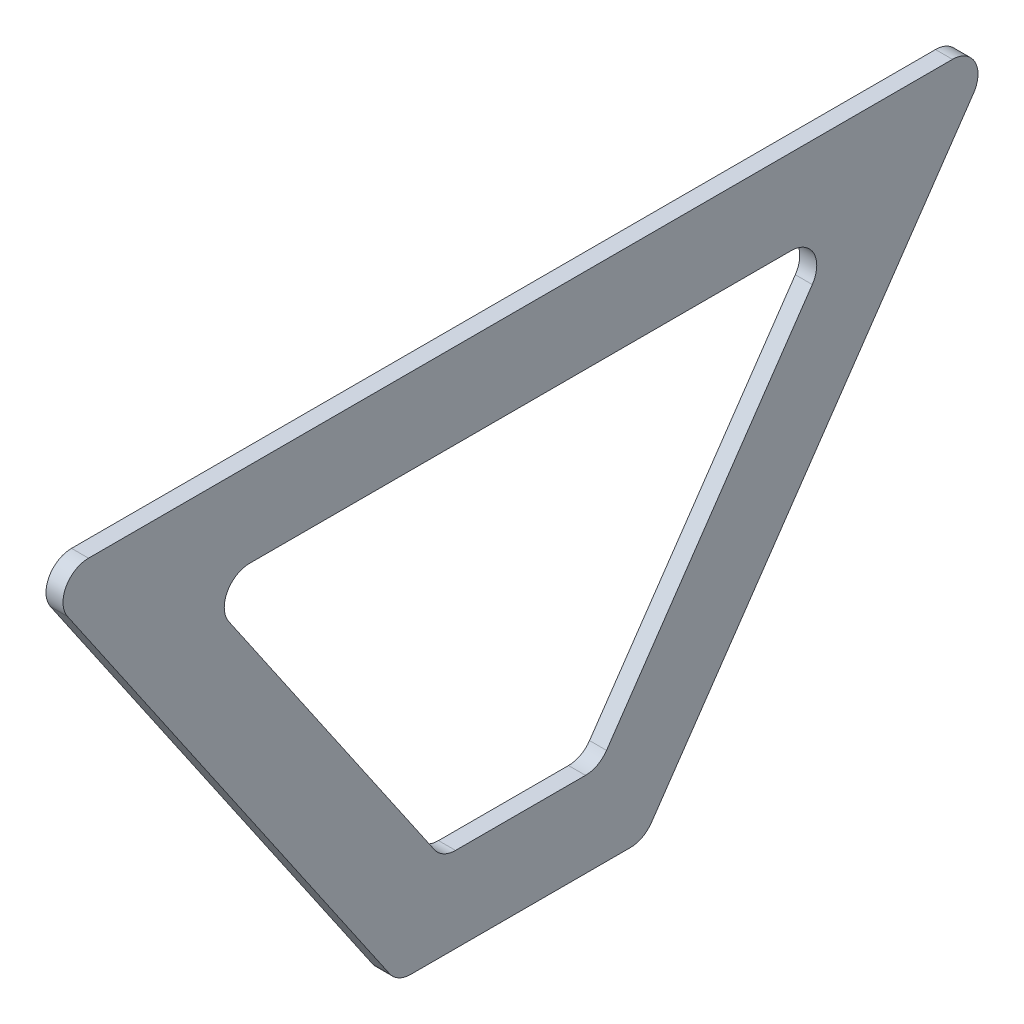
SolidWorks part; units mm, degrees
material "Acrylic (Medium-high impact)"
ref_plane "Front Plane" through (0, 0, 0) normal (0, 0, 1) x (1, 0, 0)
ref_plane "Top Plane" through (0, 0, 0) normal (0, 1, 0) x (1, 0, 0)
ref_plane "Right Plane" through (0, 0, 0) normal (1, 0, 0) x (0, 0, -1)
sketch "Sketch1" plane through (0, 0, 0) normal (1, 0, 0) x (0, 0, -1)
  line L0 (0, 24.4397) -> (0, -31.8822) construction
  line L1 (-14.5, -22.0259) -> (14.5, -22.0259)
  line L2 (14.5, -22.0259) -> (56.5, 39.3247)
  line L3 (56.5, 39.3247) -> (-56.5, 39.3247)
  line L4 (-9.2271, -12.0259) -> (9.2271, -12.0259)
  line L5 (9.2271, -12.0259) -> (37.5353, 29.3247)
  line L6 (37.5353, 29.3247) -> (-37.5353, 29.3247)
  line L7 (-9.2271, -12.0259) -> (-37.5353, 29.3247)
  line L8 (-14.5, -22.0259) -> (-56.5, 39.3247)
  point P13 (0, 29.3247)
  point P14 (0, -12.0259)
  point P15 (0, 39.3247)
  point P16 (0, -22.0259)
  dimension "D1" = 14.5
  dimension "D2" = 56.5
  dimension "D3" = 10
  dimension "D4" = 10
  dimension "D5" = 10
base flange "Base-Flange1" sketch "Sketch1" thickness 2 reverse thickness direction no parameters "D1"=10
fillet "Fillet1" radius 3 8 edges at (-1, 29.3247, -37.5353) (-1, 29.3247, 37.5353) (-1, -12.0259, -9.2271) (-1, -12.0259, 9.2271) (-1, -22.0259, 14.5) (-1, -22.0259, -14.5) (-1, 39.3247, -56.5) (-1, 39.3247, 56.5)
sketch "Bend-Lines1" [suppressed] plane through (0, 0, 0) normal (0, 1, 0) x (1, 0, 0)
sketch "Bounding-Box1" [suppressed] plane through (0, 0, 0) normal (0, 1, 0) x (1, 0, 0)
sheet metal parameters "Sheet-Metal1" thickness 2 parameters "D1"=10
flat pattern "Flat-Pattern1" [suppressed]
sketch "Bend-Lines2" plane through (0, 0, 0) normal (0, 1, 0) x (1, 0, 0)
sketch3d "Bounding-Box2" [suppressed]
  line L0 (-53.8106, -22.0259, 0) -> (53.8106, -22.0259, 0) construction
  line L1 (-53.8106, 39.3247, 0) -> (53.8106, 39.3247, 0) construction
  line L2 (-53.8106, -22.0259, 0) -> (-53.8106, 39.3247, 0) construction
  line L3 (53.8106, -22.0259, 0) -> (53.8106, 39.3247, 0) construction
